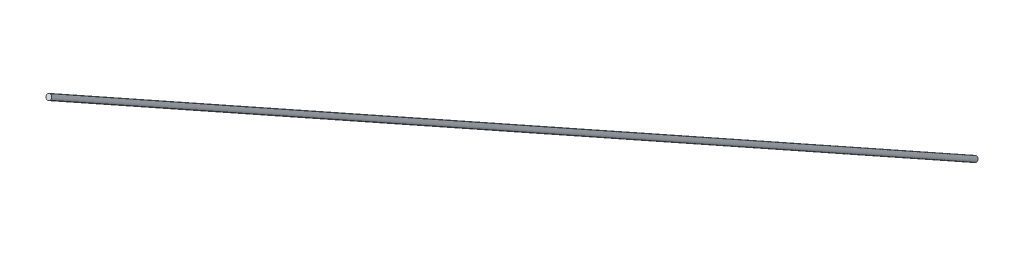
SolidWorks part; units mm, degrees
ref_plane "Front Plane" through (0, 0, 0) normal (0, 0, 1) x (1, 0, 0)
ref_plane "Top Plane" through (0, 0, 0) normal (0, 1, 0) x (1, 0, 0)
ref_plane "Right Plane" through (0, 0, 0) normal (1, 0, 0) x (0, 0, -1)
sketch3d "3DSketch1"
  line L0 (285.4746, 350.6152, -782.7736) -> (285.4746, 189.7202, -1071.1221) construction
  line L1 (285.4746, 350.6152, -782.7736) -> (285.4746, 189.7202, -1071.1221)
sweep "Sweep1" add path "3DSketch1" circular profile diameter 1.5875 parameters "D3"=1.5875
